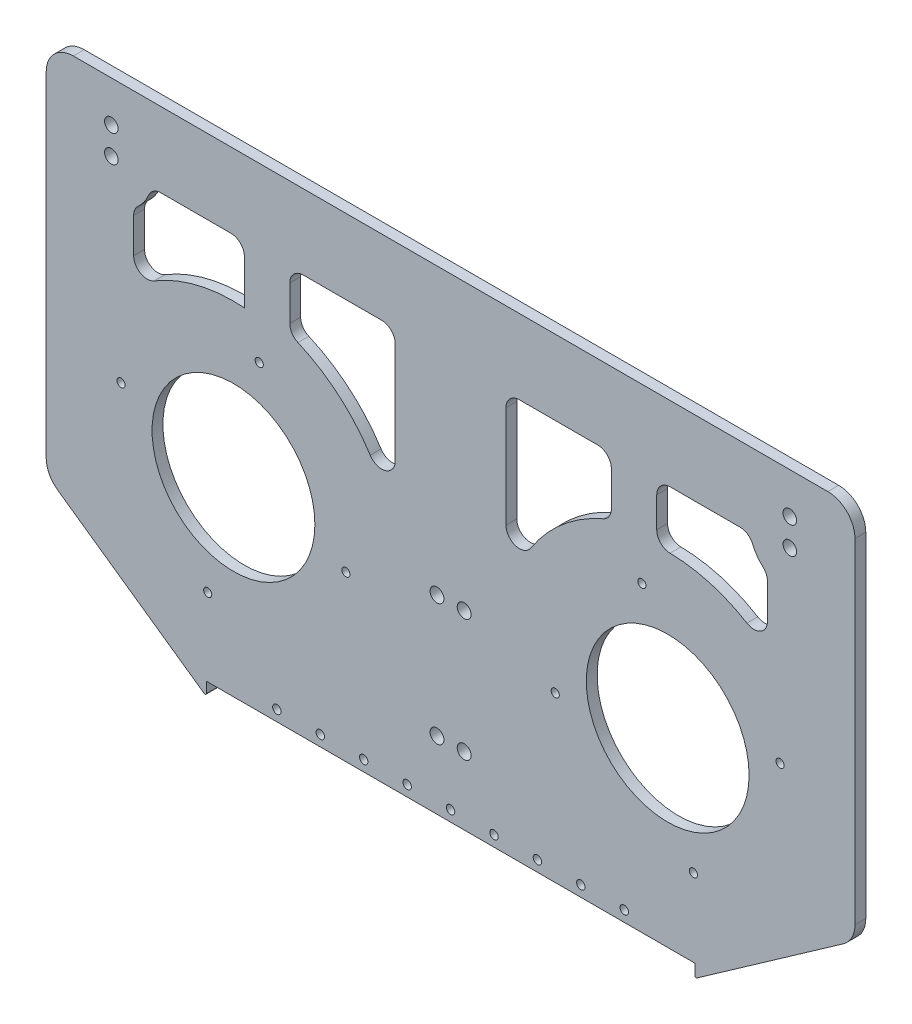
SolidWorks part; units mm, degrees
ref_plane "Front Plane" through (0, 0, 0) normal (0, 0, 1) x (1, 0, 0)
ref_plane "Top Plane" through (0, 0, 0) normal (0, 1, 0) x (1, 0, 0)
ref_plane "Right Plane" through (0, 0, 0) normal (1, 0, 0) x (0, 0, -1)
sketch "Sketch1" plane through (0, 0, 0) normal (0, 0, 1) x (1, 0, 0)
  line L0 (-125, 100) -> (125, 100) construction
  line L1 (-125, 0) -> (125, 0) construction
  line L2 (-145, -16.3871) -> (-90, -55) construction
  line L3 (-90, -55) -> (90, -55)
  line L4 (90, -55) -> (145, -16.3871) construction
  line L5 (-125, 105) -> (-125, 95) construction
  line L6 (0, -55) -> (0, 100) construction
  line L7 (-145, 120) -> (145, 120)
  line L8 (145, 120) -> (145, -16.3871) construction
  line L11 (-145, -16.3871) -> (-145, 120) construction
  line L12 (125, 105) -> (125, 95) construction
  line L14 (-149, 120) -> (-149, -18.4662)
  line L15 (-149, -18.4662) -> (-90, -59.8873)
  line L16 (-90, -59.8873) -> (-90, -55)
  line L17 (-90, -59.8873) -> (-90, -55)
  line L18 (-149, 120) -> (-145, 120)
  line L19 (90, -59.8873) -> (90, -55)
  line L20 (149, 120) -> (145, 120)
  line L21 (149, -18.4662) -> (90, -59.8873)
  line L22 (149, 120) -> (149, -18.4662)
  circle A0 centre (-125, 100) radius 12.5 construction
  circle A10 centre (-125, 0) radius 12.5 construction
  circle A11 centre (125, 0) radius 12.5 construction
  circle A12 centre (-125, 0) radius 17.5 construction
  circle A13 centre (-125, 100) radius 17.5 construction
  circle A25 centre (-125, 95) radius 2.5
  circle A26 centre (-125, 105) radius 2.5
  circle A27 centre (125, 95) radius 2.5
  circle A28 centre (125, 105) radius 2.5
  circle A32 centre (5, 15) radius 2.55
  circle A33 centre (5, -30) radius 2.55
  circle A34 centre (-5, -30) radius 2.55
  circle A35 centre (-5, 15) radius 2.55
  point P12 (0, 100)
  point P15 (0, -34.3933)
  point P45 (0, 120)
  dimension "D1" = 25
  dimension "D2" = 5
  dimension "D17" = 5.1
  dimension "D4" = 100
  dimension "D6" = 5
  dimension "D11" = 20
  dimension "D12" = 20
  dimension "D7" = 10
  dimension "D8" = 250
  dimension "D9" = 180
  dimension "D10" = 144.929
  dimension "D13" = 4
  dimension "D14" = 4
  dimension "D15" = 5
  dimension "D16" = 45
  dimension "D3" = 25
  dimension "D18" = 175
extrude "Boss-Extrude1" add sketch "Sketch1" along normal blind 4 contours L22 L20 L7 L18 L14 L15 L16 L3 L19 L21 A27 A26 A25 A28 region at (0, 35.2559, 0)
sketch "Sketch2" plane through (0, 0, 4) normal (0, 0, 1) x (1, 0, 0)
  line L0 (121.4264, 24.4924) -> (38.5736, 5.5076) construction
  line L1 (89.4924, -26.4264) -> (70.5076, 56.4264) construction
  line L2 (0, 0) -> (0, 120) construction
  line L5 (-80, 15) -> (80, 15) construction
  line L6 (-5, 15) -> (5, 15) construction
  line L8 (-149, 120) -> (-149, -18.4662) construction
  line L9 (149, 120) -> (-149, 120) construction
  circle A0 centre (80, 15) radius 42.5 construction
  circle A1 centre (38.5736, 5.5076) radius 1.5
  circle A2 centre (70.5076, 56.4264) radius 1.5
  circle A3 centre (121.4264, 24.4924) radius 1.5
  circle A4 centre (89.4924, -26.4264) radius 1.5
  circle A5 centre (80, 15) radius 30
  circle A6 centre (-38.5736, 5.5076) radius 1.5
  circle A7 centre (-70.5076, 56.4264) radius 1.5
  circle A8 centre (-89.4924, -26.4264) radius 1.5
  circle A9 centre (-121.4264, 24.4924) radius 1.5
  circle A10 centre (-80, 15) radius 42.5 construction
  circle A11 centre (-80, 15) radius 30
  circle A12 centre (-80, 15) radius 47.5 construction
  point P6 (80, 15)
  point P27 (-80, 15)
  point P30 (0, 15)
  dimension "D1" = 85
  dimension "D2" = 3
  dimension "D3" = 60
  dimension "D4" = 95
  dimension "D5" = 69
  dimension "D6" = 41.4264
  dimension "D7" = 105
  dimension "D8" = 10
extrude "Cut-Extrude1" cut sketch "Sketch2" against normal blind 10 contours A11 | A5 | A7 | A9 | A8 | A2 | A1 | A3 | A4 | A6 region at (38.5736, 5.5076, 4) region at (70.5076, 56.4264, 4) region at (121.4264, 24.4924, 4) region at (89.4924, -26.4264, 4) region at (80, 15, 4) region at (-70.5076, 56.4264, 4) region at (-89.4924, -26.4264, 4) region at (-121.4264, 24.4924, 4) region at (-80, 15, 4)
sketch "Sketch3" plane through (0, 0, 4) normal (0, 0, 1) x (1, 0, 0)
  line L1 (-90, -59.8873) -> (-90, -55) construction
  line L3 (-90, -55) -> (90, -55) construction
  circle A4 centre (-64, -51) radius 1.55
  circle A5 centre (-48, -51) radius 1.55
  circle A6 centre (-32, -51) radius 1.55
  circle A7 centre (-16, -51) radius 1.55
  circle A8 centre (0, -51) radius 1.55
  circle A9 centre (16, -51) radius 1.55
  circle A10 centre (32, -51) radius 1.55
  circle A11 centre (48, -51) radius 1.55
  circle A12 centre (64, -51) radius 1.55
  dimension "D2" = 3.1
  dimension "D1" = 4
  dimension "D3" = 26
  dimension "D5" = 9
extrude "Cut-Extrude2" cut sketch "Sketch3" against normal through all contours A4 | A5 | A6 | A12 | A11 | A10 | A7 | A8 | A9 region at (-64, -51, 4) region at (-48, -51, 4) region at (-32, -51, 4) region at (32, -51, 4) region at (48, -51, 4) region at (64, -51, 4)
sketch "Sketch6" plane through (0, 0, 0) normal (0, 0, -1) x (-1, 0, 0)
  line L0 (-20.3921, 20.3957) -> (-20.3921, 92.4562)
  line L1 (-20.3921, 92.4562) -> (-59.2398, 92.4562)
  line L2 (-59.2398, 92.4562) -> (-59.2398, 71.1358)
  line L3 (-75.9623, 92.4562) -> (-110.4197, 92.4562)
  line L4 (-75.9623, 92.4562) -> (-75.9623, 71.1358)
  line L5 (-116.7764, 82.6944) -> (-116.7764, 57.603)
  line L6 (0, -55) -> (0, 120) construction
  line L7 (90, -55) -> (-90, -55) construction
  line L8 (-145, 120) -> (145, 120) construction
  line L9 (20.3921, 20.3957) -> (20.3921, 92.4562)
  line L10 (20.3921, 92.4562) -> (59.2398, 92.4562)
  line L11 (59.2398, 92.4562) -> (59.2398, 71.1358)
  line L12 (75.9623, 92.4562) -> (75.9623, 71.1358)
  line L13 (75.9623, 92.4562) -> (110.4197, 92.4562)
  line L14 (116.7764, 82.6944) -> (116.7764, 57.603)
  arc A0 (-20.3921, 20.3957) -> (-59.2398, 71.1358) centre (-80, 15) ccw
  arc A1 (-75.9623, 71.1358) -> (-116.7764, 57.603) centre (-80, 15) ccw
  arc A2 (-110.4197, 92.4562) -> (-116.7764, 82.6944) centre (-125, 95) cw
  arc A3 (20.3921, 20.3957) -> (59.2398, 71.1358) centre (80, 15) cw
  arc A4 (75.9623, 71.1358) -> (116.7764, 57.603) centre (80, 15) cw
  arc A5 (110.4197, 92.4562) -> (116.7764, 82.6944) centre (125, 95) ccw
extrude "Cut-Extrude3" cut sketch "Sketch6" against normal through all contours L3 A2 L5 A1 L4 | A0 L0 L1 L2 | L9 A3 L11 L10 | A5 L13 L12 A4 L14 region at (36.1386, 72.1325, 0) region at (97.4759, 79.2288, 0) region at (-36.1386, 72.1325, 0) region at (-97.4759, 79.2288, 0)
fillet "Fillet1" radius 5 17 edges at (-59.2398, 92.4562, 2) (-110.4197, 92.4562, 2) (-116.7764, 82.6944, 2) (-59.2398, 71.1358, 2) (-116.7764, 57.603, 2) (-75.9623, 92.4562, 2) (-20.3921, 92.4562, 2) (-20.3921, 20.3957, 2) (20.3921, 20.3957, 2) (59.2398, 92.4562, 2) (59.2398, 71.1358, 2) (20.3921, 92.4562, 2) (75.9623, 92.4562, 2) (75.9623, 71.1358, 2) (110.4197, 92.4562, 2) (116.7764, 82.6944, 2) (116.7764, 57.603, 2)
fillet "Fillet2" radius 0.5 2 edges at (90, -59.8873, 2) (-90, -59.8873, 2)
fillet "Fillet3" radius 10 4 edges at (149, -18.4662, 2) (149, 120, 2) (-149, 120, 2) (-149, -18.4662, 2)
equation "\"D1@Sketch1\" = \"cf_tube_outer_diameter\""
equation "\"mid_plate_mid_to_top\" = 100mm"
equation "\"mid_plate_mid_to_bottom\" = 30mm"
equation "\"mid_plate_horizontal_spacing\"=250mm"
equation "\"cf_tube_outer_diameter\"= 25mm"
equation "\"D4@Sketch1\"=\"mid_plate_mid_to_top\""
equation "\"cf_tube_inner_diameter\" = 21mm"
equation "\"mid_tube_length\" = 121mm"
equation "\"cf_plate_thickness\" =4mm"
equation "\"D1@Boss-Extrude1\"=\"cf_plate_thickness\""
equation "\"D8@Sketch1\"=\"mid_plate_horizontal_spacing\""
equation "\"mid_plate_bottom_width\" = 180mm"
equation "\"D9@Sketch1\"=\"mid_plate_bottom_width\""
equation "\"mid_support_plate_distance\" = 250mm"
equation "\"nut_strip_2_hole_distance\" = 7mm"
equation "\"nut_strip_hole_diameter\" = 2.5mm"
equation "\"nut_strip_hole_to_edge_distance\"= 2.5mm"
